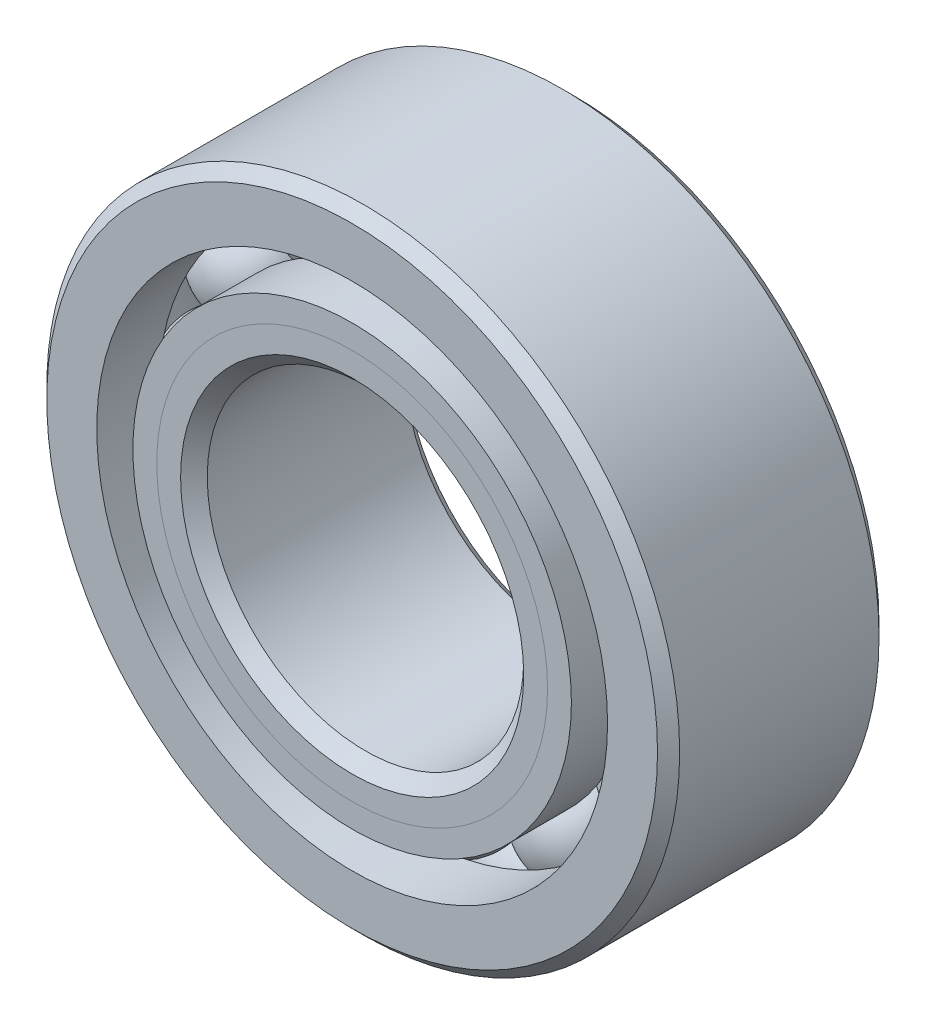
SolidWorks part; units mm, degrees
ref_plane "Front Plane" through (0, 0, 0) normal (0, 0, 1) x (1, 0, 0)
ref_plane "Top Plane" through (0, 0, 0) normal (0, 1, 0) x (1, 0, 0)
ref_plane "Right Plane" through (0, 0, 0) normal (1, 0, 0) x (0, 0, -1)
sketch "Sketch1" plane through (0, 0, 0) normal (1, 0, 0) x (0, 0, -1)
  line L0 (-1.3891, 0) -> (1.3891, 0) construction
  line L1 (0, 3.9688) -> (0, -3.9688) construction
  line L2 (1.2502, 3.9688) -> (-1.2502, 3.9688)
  line L3 (-1.2502, 3.9688) -> (-1.3891, 3.8298)
  line L4 (-1.3891, 3.8298) -> (-1.3891, 3.2033)
  line L5 (-1.3891, 3.2033) -> (-0.6174, 3.2033)
  line L6 (1.3891, 3.2033) -> (0.6174, 3.2033)
  line L7 (1.3891, 3.8298) -> (1.3891, 3.2033)
  line L8 (1.2502, 3.9688) -> (1.3891, 3.8298)
  line L9 (0, 3.9688) -> (0, 2.9766) construction
  line L10 (0, 2.9766) -> (0, 1.9844) construction
  arc A0 (-0.6174, 3.2033) -> (0.6174, 3.2033) centre (0, 2.9766) cw
  point P14 (0, 1.9844)
  dimension "Width" = 2.7781
  dimension "OD" = 7.9375
  dimension "D1" = 45
  dimension "D2" = 0.1389
  dimension "D3" = 1.2347
  dimension "D4" = 0.2268
revolve "Revolve1" add sketch "Sketch1" angle 360 about L0
sketch "Sketch2" plane through (0, 0, 0) normal (1, 0, 0) x (0, 0, -1)
  line L0 (-1.3891, 2.7498) -> (-0.6174, 2.7498)
  line L1 (-1.3891, 3.8298) -> (-1.3891, -3.8298) construction
  line L2 (-1.3891, 2.7498) -> (-1.3891, 2.4507)
  line L3 (-1.3891, 2.4507) -> (-1.09, 2.1516)
  line L4 (-1.09, 2.1516) -> (0, 2.1516)
  line L5 (0, 3.9688) -> (0, -3.9688) construction
  line L6 (0, 2.1516) -> (0, 2.3189)
  line L7 (0, 2.3189) -> (0, 1.9844) construction
  line L8 (-1.3891, 2.7498) -> (-1.3891, 2.1516) construction
  line L9 (-1.3891, 2.1516) -> (-1.09, 2.1516) construction
  arc A0 (-0.6174, 2.7498) -> (0, 2.3189) centre (0, 2.9766) ccw
  arc A1 (0.6174, 3.2033) -> (-0.6174, 3.2033) centre (0, 2.9766) ccw construction
  circle A2 centre (0, 2.9766) radius 0.6577 construction
  dimension "D1" = 45
revolve "Revolve2" add sketch "Sketch2" angle 360 about L0
sketch "Sketch3" plane through (0, 0, 0) normal (1, 0, 0) x (0, 0, -1)
  line L0 (-1.3891, 2.4507) -> (-1.09, 2.1516)
  line L1 (-1.09, 2.1516) -> (0, 2.1516)
  line L2 (0, 2.1516) -> (0, 2.3189)
  line L3 (-1.3891, 2.4507) -> (-1.3891, 2.1516)
  line L4 (-1.3891, 2.7498) -> (-1.3891, 2.1516) construction
  line L5 (-1.3891, 2.1516) -> (-1.2218, 1.9844)
  line L6 (-1.2218, 1.9844) -> (1.2502, 1.9844)
  line L7 (1.2502, 3.9688) -> (1.2502, -3.9688) construction
  line L8 (1.2502, 1.9844) -> (1.3891, 2.1233)
  line L9 (1.3891, -3.8298) -> (1.3891, 3.8298) construction
  line L10 (1.3891, 2.1233) -> (1.3891, 2.7498)
  line L11 (1.3891, 2.7498) -> (0.6174, 2.7498)
  line L13 (1.2502, 3.9688) -> (1.3891, 3.8298) construction
  circle A0 centre (0, 2.9766) radius 0.6577 construction
  arc A1 (0.6174, 2.7498) -> (0, 2.3189) centre (0, 2.9766) cw
revolve "Revolve3" add sketch "Sketch3" angle 360 about L0
sketch "Sketch4" plane through (0, 0, 0) normal (1, 0, 0) x (0, 0, -1)
  line L0 (-0.6577, 2.9766) -> (0.6577, 2.9766)
  circle A1 centre (0, 2.9766) radius 0.6577 construction
  arc A2 (-0.6577, 2.9766) -> (0.6577, 2.9766) centre (0, 2.9766) cw
  arc A3 (0.6174, 3.2033) -> (-0.6174, 3.2033) centre (0, 2.9766) ccw construction
revolve "Revolve4" add sketch "Sketch4" angle 360 about L0
ref_axis "Axis1" through (0, 0, -1.3891) along (0, 0, 1)
pattern_circular "CirPattern1" count 12 every 30 about axis through (0, 0, -1.3891) along (0, 0, 1) of bodies 104
equation "\"D2@Sketch1\" = \"Width@Sketch1\"*.05"
equation "\"D3@Sketch1\" = \"Width@Sketch1\"/2.25"
equation "\"D4@Sketch1\" = (((\"OD@Sketch1\"-\"Width@Sketch1\")/2)/3.25)/3.5"
equation "\"D2@CirPattern1\" = 360/\"Balls@CirPattern1\""
